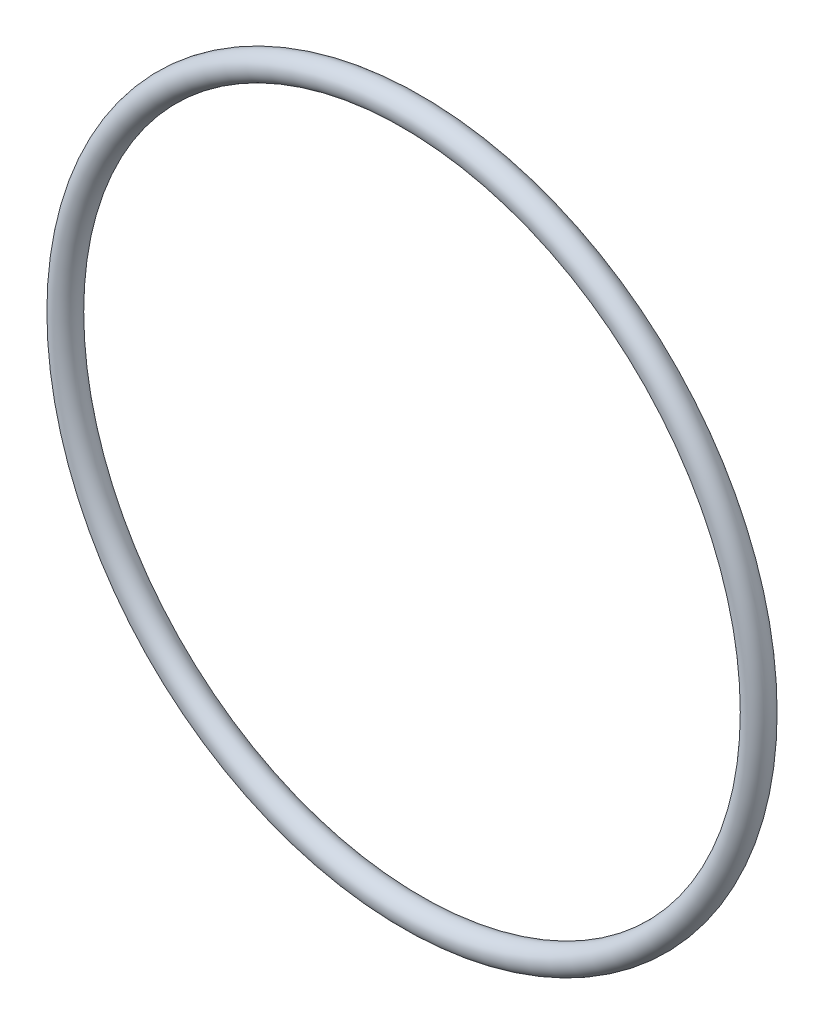
SolidWorks part; units mm, degrees
ref_plane "Front" through (0, 0, 0) normal (0, 0, 1) x (1, 0, 0)
ref_plane "Top" through (0, 0, 0) normal (0, 1, 0) x (1, 0, 0)
ref_plane "Right" through (0, 0, 0) normal (1, 0, 0) x (0, 0, -1)
sketch "Sketch1" plane through (0, 0, 0) normal (1, 0, 0) x (0, -1, 0)
  line L0 (0, -1.25) -> (0, 1.25) construction
  line L2 (-37.95, 0) -> (37.95, 0) construction
  line L3 (-32, 0) -> (32, 0) construction
  circle A0 centre (33.25, 0) radius 1.25
  point P9 (32, 0)
  point P10 (34.5, 0)
  point P13 (33.25, 1.25)
  point P14 (33.25, -1.25)
  dimension "Width" = 2.5
  dimension "ID" = 64
revolve "Revolve1" add sketch "Sketch1" angle 360 about L0
ref_axis "Axis1" through (0, 0, -1.375) along (0, 0, 1)
